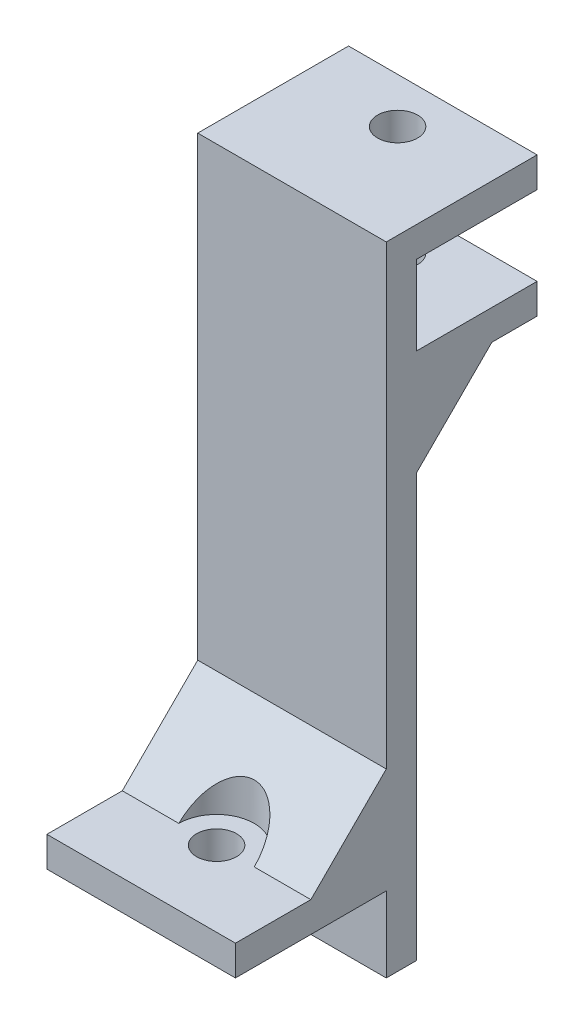
SolidWorks part; units mm, degrees
ref_plane "Front Plane" through (0, 0, 0) normal (0, 0, 1) x (1, 0, 0)
ref_plane "Top Plane" through (0, 0, 0) normal (0, 1, 0) x (1, 0, 0)
ref_plane "Right Plane" through (0, 0, 0) normal (1, 0, 0) x (0, 0, -1)
sketch "Sketch1" plane through (0, 0, 0) normal (1, 0, 0) x (0, 0, -1)
  line L0 (0, 0) -> (0, 10)
  line L1 (4, 70) -> (20, 70)
  line L7 (0, 84.525) -> (20, 84.525)
  line L8 (20, 84.525) -> (20, 80.525)
  line L9 (20, 80.525) -> (4, 80.525)
  line L10 (4, 80.525) -> (4, 70)
  line L11 (0, 14) -> (-20, 14)
  line L12 (-20, 14) -> (-20, 10)
  line L13 (-20, 10) -> (0, 10)
  line L14 (0, 14) -> (0, 84.525)
  line L15 (20, 70) -> (20, 66)
  line L16 (20, 66) -> (4, 66)
  line L17 (4, 66) -> (4, 0)
  line L18 (4, 0) -> (0, 0)
  dimension "D1" = 20
  dimension "D2" = 20
  dimension "D3" = 4
  dimension "D4" = 4
  dimension "D5" = 10.525
  dimension "D6" = 4
  dimension "D7" = 60
  dimension "D8" = 10
  dimension "D9" = 4
  dimension "D10" = 4
extrude "Boss-Extrude1" add sketch "Sketch1" along normal blind 25
sketch "Sketch2" plane through (0, 14, 0) normal (0, 1, 0) x (1, 0, 0)
  line L0 (12.5, 0) -> (12.5, -20) construction
  line L1 (25, 0) -> (0, 0) construction
  line L2 (25, -20) -> (0, -20) construction
  circle A0 centre (12.5, -10) radius 2.65
  dimension "D1" = 5.3
  dimension "D2" = 10
extrude "Cut-Extrude1" cut sketch "Sketch2" against normal blind 6 and the other way blind 6
sketch "Sketch3" plane through (0, 84.525, 0) normal (0, 1, 0) x (1, 0, 0)
  line L0 (12.5, 20) -> (12.5, 0) construction
  line L1 (25, 20) -> (0, 20) construction
  line L2 (25, 0) -> (0, 0) construction
  circle A0 centre (12.5, 14) radius 2.65
  dimension "D1" = 5.3
  dimension "D2" = 14
extrude "Cut-Extrude2" cut sketch "Sketch3" against normal through all
chamfer "Chamfer1" distance 10 angle 45 1 edges at (12.5, 14, 0)
sketch "Sketch4" plane through (0, 14, 0) normal (0, 1, 0) x (1, 0, 0)
  circle A0 centre (12.5, -10) radius 5
  dimension "D1" = 10
extrude "Cut-Extrude4" cut sketch "Sketch4" along normal blind 6
chamfer "Chamfer2" distance 10 angle 45 1 edges at (12.5, 66, -4)
sketch "Sketch5" plane through (0, 66, 0) normal (0, -1, 0) x (1, 0, 0)
  circle A0 centre (12.5, -14) radius 5
  dimension "D1" = 10
extrude "Cut-Extrude5" cut sketch "Sketch5" along normal blind 6
